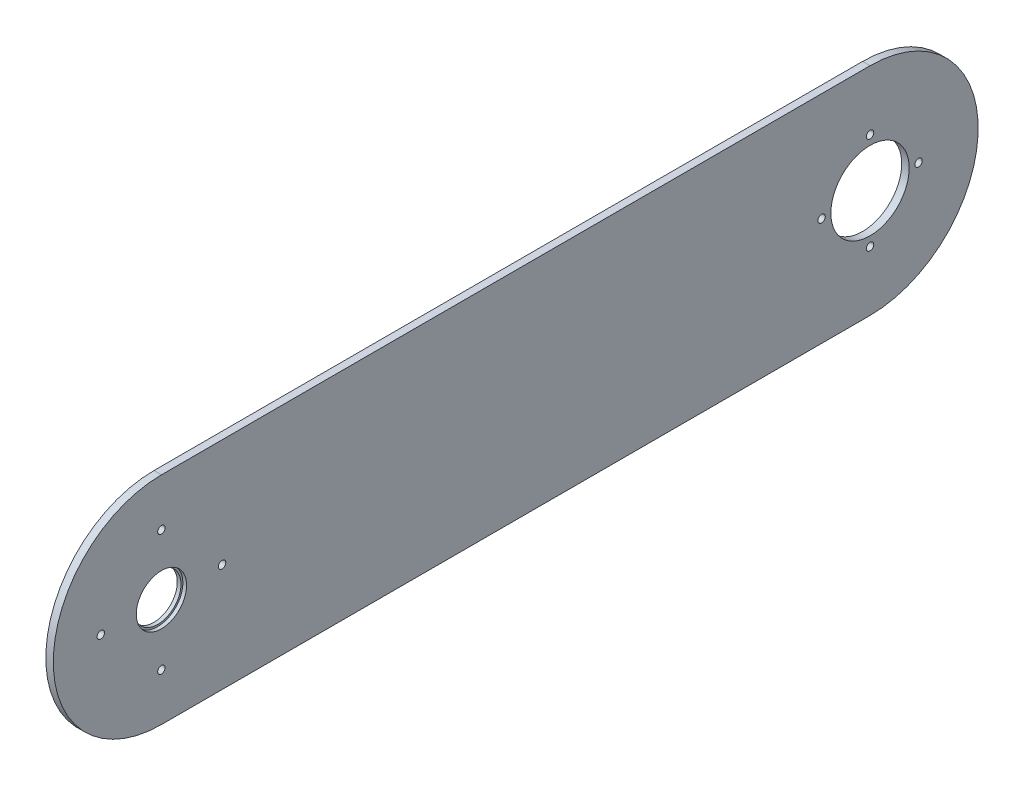
SolidWorks part; units mm, degrees
ref_plane "Front Plane" through (0, 0, 0) normal (0, 0, 1) x (1, 0, 0)
ref_plane "Top Plane" through (0, 0, 0) normal (0, 1, 0) x (1, 0, 0)
ref_plane "Right Plane" through (0, 0, 0) normal (1, 0, 0) x (0, 0, -1)
sketch "Sketch1" plane through (0, 0, 0) normal (1, 0, 0) x (0, 0, -1)
  line L0 (0, 0) -> (380, 0) construction
  line L1 (0, 58) -> (380, 58)
  line L2 (0, -58) -> (380, -58)
  circle A0 centre (0, 0) radius 24
  arc A1 (0, 58) -> (0, -58) centre (0, 0) ccw
  arc A2 (380, -58) -> (380, 58) centre (380, 0) ccw
  circle A3 centre (380, 0) radius 24
  point P3 (190, 0)
  dimension "D1" = 58
  dimension "D2" = 48
  dimension "D3" = 380
extrude "Boss-Extrude1" add sketch "Sketch1" along normal blind 4
sketch "Sketch2" plane through (0, 0, 0) normal (-1, 0, 0) x (0, 0, 1)
  circle A0 centre (0, 0) radius 29
  dimension "D1" = 58
extrude "Cut-Extrude1" [suppressed] cut sketch "Sketch2" against normal blind 2
sketch "Sketch3" plane through (0, 0, 0) normal (-1, 0, 0) x (0, 0, 1)
  line L0 (58, 0) -> (58, 58) construction
  line L1 (58, 58) -> (-67, 58) construction
  line L2 (-380, 58) -> (0, 58) construction
  line L3 (0, -58) -> (-380, -58) construction
  line L4 (-67, 58) -> (-71, 58) construction
  line L5 (-67, 58) -> (-67, -58) construction
  line L6 (-67, -58) -> (-71, -58) construction
  line L7 (-71, 58) -> (-71, -58) construction
  line L8 (-67, 0) -> (-60, 0) construction
  line L9 (-69, 58) -> (-69, 36.6334) construction
  arc A0 (0, -58) -> (0, 58) centre (0, 0) ccw construction
  circle A1 centre (-60, 51) radius 2
  circle A2 centre (-78, 51) radius 2
  circle A3 centre (-60, -51) radius 2
  circle A4 centre (-78, -51) radius 2
  dimension "D3" = 4
  dimension "D1" = 125
  dimension "D2" = 4
  dimension "D4" = 7
  dimension "D5" = 7
extrude "Cut-Extrude2" [suppressed] cut sketch "Sketch3" against normal through all
sketch "Sketch4" plane through (0, 0, 0) normal (-1, 0, 0) x (0, 0, 1)
  circle A0 centre (0, 0) radius 32.5 construction
  circle A1 centre (0, 32.5) radius 2
  circle A2 centre (32.5, 0) radius 2
  circle A3 centre (0, -32.5) radius 2
  circle A4 centre (-32.5, 0) radius 2
  point P13 (0, 0)
  dimension "D1" = 65
  dimension "D2" = 4
  dimension "D3" = 4
extrude "Cut-Extrude3" cut sketch "Sketch4" against normal through all
sketch "Sketch5" plane through (0, 0, 0) normal (-1, 0, 0) x (0, 0, 1)
  circle A0 centre (0, 0) radius 24 construction
  circle A1 centre (0, 0) radius 24
  circle A2 centre (0, 0) radius 12.5
  dimension "D1" = 25
extrude "Boss-Extrude2" add sketch "Sketch5" against normal up to surface (4 mm away) up to face at (4, 32.5, 2)
sketch "Sketch6" plane through (4, 0, 0) normal (1, 0, 0) x (0, 0, -1)
  circle A0 centre (0, 0) radius 13.5
  dimension "D1" = 27
extrude "Cut-Extrude4" cut sketch "Sketch6" against normal blind 2
sketch "Sketch7" plane through (0, 0, 0) normal (-1, 0, 0) x (0, 0, 1)
  circle A1 centre (-380, 0) radius 21
  circle A2 centre (-380, 0) radius 24 construction
  circle A3 centre (-380, 0) radius 24
  dimension "D1" = 42
extrude "Boss-Extrude3" add sketch "Sketch7" against normal up to surface (4 mm away) up to face at (4, 0, -13.5)
sketch "Sketch8" plane through (0, 0, 0) normal (-1, 0, 0) x (0, 0, 1)
  circle A0 centre (-380, 0) radius 26 construction
  circle A1 centre (-380, 26) radius 2
  circle A2 centre (-354, 0) radius 2
  circle A3 centre (-380, -26) radius 2
  circle A4 centre (-406, 0) radius 2
  point P14 (-380, 0)
  dimension "D1" = 52
  dimension "D2" = 4
  dimension "D3" = 4
extrude "Cut-Extrude5" cut sketch "Sketch8" against normal through all
